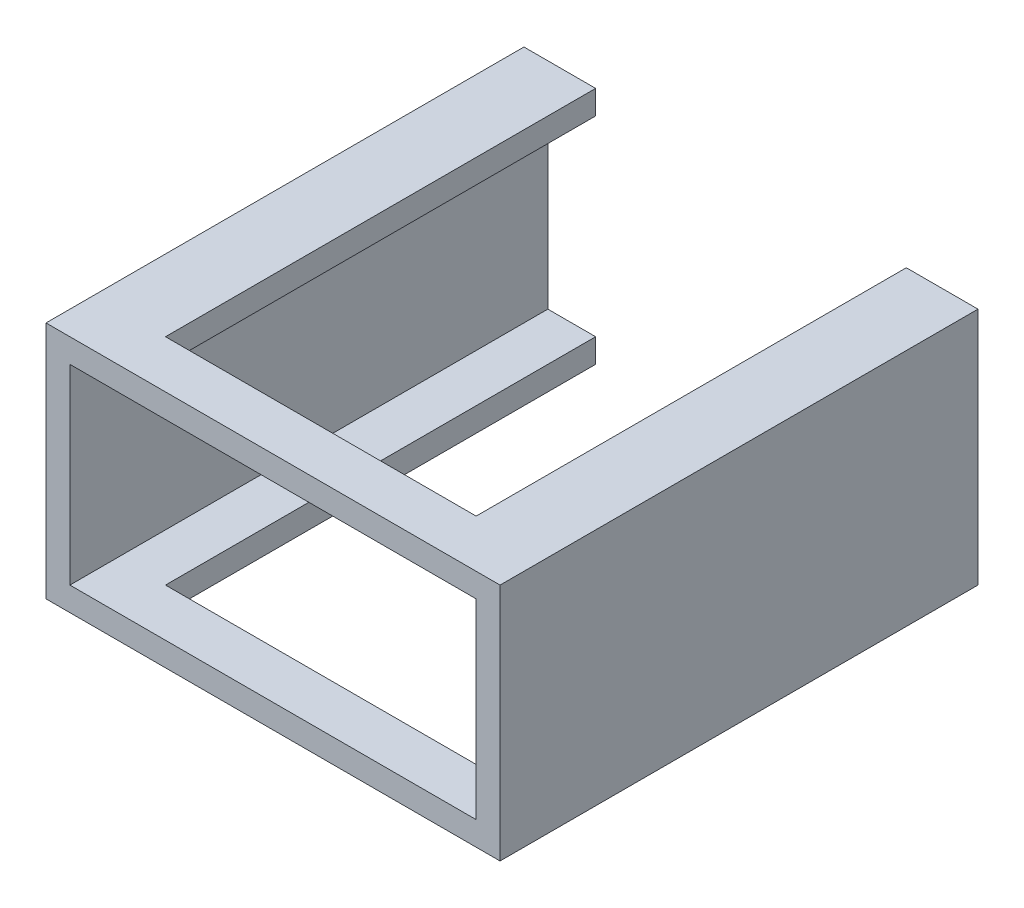
SolidWorks part; units mm, degrees
ref_plane "Front Plane" through (0, 0, 0) normal (0, 0, 1) x (1, 0, 0)
ref_plane "Top Plane" through (0, 0, 0) normal (0, 1, 0) x (1, 0, 0)
ref_plane "Right Plane" through (0, 0, 0) normal (1, 0, 0) x (0, 0, -1)
sketch "Sketch1" plane through (0, 0, 0) normal (0, 0, 1) x (1, 0, 0)
  line L1 (-9.6301, 7.2226) -> (9.3699, 7.2226)
  line L2 (-9.6301, 7.2226) -> (-9.6301, -2.7774)
  line L3 (-9.6301, -2.7774) -> (9.3699, -2.7774)
  line L4 (9.3699, 7.2226) -> (9.3699, -2.7774)
  dimension "D1" = 19
  dimension "D2" = 10
extrude "Boss-Extrude1" add sketch "Sketch1" along normal blind 10 and the other way blind 10
sketch "Sketch2" plane through (0, 0, 10) normal (0, 0, 1) x (1, 0, 0)
  line L0 (-0.1301, 7.2226) -> (-0.1301, -2.7774) construction
  line L1 (-8.6301, 6.2226) -> (8.3699, 6.2226)
  line L2 (-8.6301, 6.2226) -> (-8.6301, -1.7774)
  line L3 (-8.6301, -1.7774) -> (8.3699, -1.7774)
  line L4 (8.3699, 6.2226) -> (8.3699, -1.7774)
  line L7 (9.3699, 7.2226) -> (-9.6301, 7.2226) construction
  line L8 (-9.6301, -2.7774) -> (9.3699, -2.7774) construction
  line L9 (-9.6301, 2.2226) -> (9.3699, 2.2226) construction
  line L10 (-9.6301, 7.2226) -> (-9.6301, -2.7774) construction
  line L11 (9.3699, -2.7774) -> (9.3699, 7.2226) construction
  dimension "D1" = 17
  dimension "D2" = 8
  dimension "D3" = 4
  dimension "D4" = 8.5
extrude "Cut-Extrude1" cut sketch "Sketch2" against normal blind 20
sketch "Sketch3" plane through (0, 0, 0) normal (0, 0, 1) x (1, 0, 0)
  line L0 (-8.6301, 6.2226) -> (-8.6301, -1.7774) construction
  line L1 (-6.6301, 7.6051) -> (6.3699, 7.6051)
  line L2 (-6.6301, 7.6051) -> (-6.6301, -2.9148)
  line L3 (-6.6301, -2.9148) -> (6.3699, -2.9148)
  line L4 (6.3699, 7.6051) -> (6.3699, -2.9148)
  line L5 (8.3699, -1.7774) -> (8.3699, 6.2226) construction
  dimension "D1" = 2
  dimension "D2" = 2
extrude "Cut-Extrude3" cut sketch "Sketch3" along normal blind 8 and the other way blind 10 contours L1 L4 L3 L2
